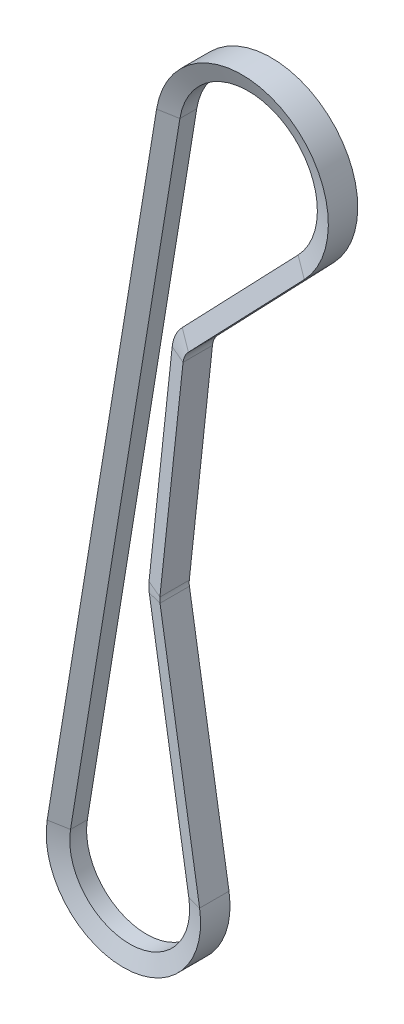
SolidWorks part; units mm, degrees
ref_plane "Front Plane" through (0, 0, 0) normal (0, 0, 1) x (1, 0, 0)
ref_plane "Top Plane" through (0, 0, 0) normal (0, 1, 0) x (1, 0, 0)
ref_plane "Right Plane" through (0, 0, 0) normal (1, 0, 0) x (0, 0, -1)
sketch "Sketch2" plane through (0, 0, 0) normal (0, 0, 1) x (1, 0, 0)
  line L0 (0, 0) -> (1, 0) construction
  line L1 (0, 0) -> (0, 1) construction
  line L12 (-24.6739, 4.025) -> (10.7432, 221.1348)
  line L14 (58.5852, 197.2447) -> (21.0573, 158.1189)
  line L15 (19.3267, 154.4045) -> (11.8168, 84.8085)
  line L16 (11.8619, 83.1118) -> (24.6783, 3.9979)
  arc A4 (10.7432, 221.1348) -> (58.5852, 197.2447) centre (38.3779, 216.6267) cw
  arc A7 (24.6783, 3.9979) -> (-24.6739, 4.025) centre (0, 0) cw
  arc A8 (21.0573, 158.1189) -> (19.3267, 154.4045) centre (25.64, 153.7233) ccw
  arc A9 (11.8168, 84.8085) -> (11.8619, 83.1118) centre (18.1301, 84.1273) ccw
ref_plane "Plane4" through (24.6783, 3.9979, 0) normal (0.1599, -0.9871, 0) x (-0.9871, -0.1599, 0)
sketch "Sketch3" plane through (24.6783, 3.9979, 0) normal (0.1599, -0.9871, 0) x (-0.9871, -0.1599, 0)
  line L0 (0, -4.7625) -> (0, 4.7625)
  line L1 (0, -4.7625) -> (5.588, -2.7286)
  line L2 (5.588, -2.7286) -> (5.588, 2.7286)
  line L3 (5.588, 2.7286) -> (0, 4.7625)
  line L4 (0, 0) -> (5.588, 0) construction
  dimension "D1" = 9.525
  dimension "D2" = 5.588
  dimension "D3" = 40
sweep "Sweep1" add profiles "Sketch3" path "Sketch2"
